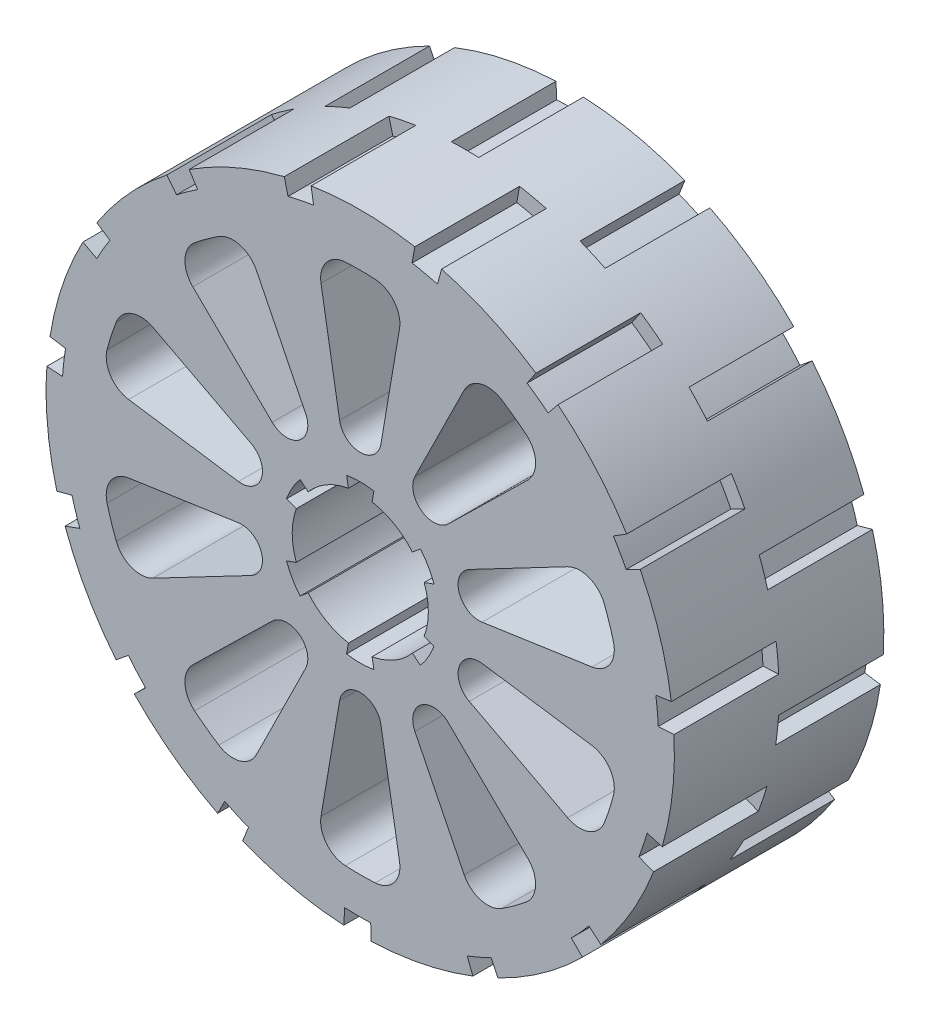
SolidWorks part; units mm, degrees
material "Silicon Rubber"
ref_plane "Plan de face" through (0, 0, 0) normal (0, 0, 1) x (1, 0, 0)
ref_plane "Plan de dessus" through (0, 0, 0) normal (0, 1, 0) x (1, 0, 0)
ref_plane "Plan de droite" through (0, 0, 0) normal (1, 0, 0) x (0, 0, -1)
sketch "Esquisse1" plane through (0, 0, 0) normal (0, 0, 1) x (1, 0, 0)
  circle A0 centre (0, 0) radius 60
  dimension "D1" = 120
extrude "Boss.-Extru.1" add sketch "Esquisse1" along normal blind 40
ref_axis "Axis1" through (0, 0, -85.4045) along (0, 0, 1)
sketch "Sketch2" plane through (0, 0, 0) normal (0, 1, 0) x (1, 0, 0)
  line L0 (0, 0) -> (-57, 0)
  line L1 (60, 0) -> (-60, 0) construction
  line L2 (-57, 0) -> (0, -15)
  line L3 (0, -15) -> (0, 0)
  line L5 (-60, 0) -> (-60, -40) construction
  dimension "D2" = 15
  dimension "D3" = 3
sketch "Sketch3" plane through (0, 0, 0) normal (0, 0, 1) x (1, 0, 0)
  line L0 (0, 60) -> (0, -60) construction
  line L1 (-3.9433, 23.1806) -> (-7.5, 44.088)
  line L2 (7.5, 44.088) -> (3.9433, 23.1806)
  circle A0 centre (0, 0) radius 60 construction
  arc A1 (-2.8565, 49.9183) -> (2.8565, 49.9183) centre (0, 0) cw
  arc A2 (7.5, 44.088) -> (2.8565, 49.9183) centre (2.5708, 44.9265) ccw
  arc A3 (-7.5, 44.088) -> (-2.8565, 49.9183) centre (-2.5708, 44.9265) cw
  arc A4 (-3.9433, 23.1806) -> (3.9433, 23.1806) centre (0, 23.8514) ccw
  point P9 (0, 50)
  dimension "D1" = 10
  dimension "D2" = 5
  dimension "D3" = 4
  dimension "D4" = 15
extrude "Cut-Extrude4" cut sketch "Sketch3" against normal through all and the other way through all
pattern_circular "CirPattern1" count 10 over 360 about axis through (0, 0, -85.4045) along (0, 0, 1) of "Cut-Extrude4"
sketch "Sketch4" plane through (0, 0, 40) normal (0, 0, 1) x (1, 0, 0)
  circle A0 centre (0, 0) radius 9
  dimension "D1" = 18
extrude "Boss-Extrude1" add sketch "Sketch4" along normal blind 10
sketch "Sketch5" plane through (0, 0, 50) normal (0, 0, 1) x (1, 0, 0)
  circle A0 centre (0, 0) radius 5
  dimension "D1" = 10
extrude "Cut-Extrude5" cut sketch "Sketch5" against normal through all
sketch "Sketch6" plane through (0, 0, 40) normal (0, 0, 1) x (1, 0, 0)
  line L0 (10.4189, 59.0885) -> (9.8979, 56.134)
  line L1 (14.7527, 55.0578) -> (15.5291, 57.9555)
  line L2 (0, 60) -> (0, 0) construction
  arc A0 (9.8979, 56.134) -> (14.7527, 55.0578) centre (0, 0) cw
  circle A1 centre (0, 0) radius 60
  arc A2 (15.5291, 57.9555) -> (10.4189, 59.0885) centre (0, 0) ccw
  circle A3 centre (0, 0) radius 60 construction
  dimension "D3" = 3
  dimension "D2" = 5
  dimension "D4" = 10
  dimension "D1" = 0
extrude "Cut-Extrude6" cut sketch "Sketch6" against normal blind 20 contours L1 A2 L0 A0 region at (12.6605, 57.1077, 40)
pattern_circular "CirPattern2" count 15 over 360 about axis through (0, 0, -85.4045) along (0, 0, 1) of "Cut-Extrude6"
sketch "Sketch7" plane through (0, 0, 0) normal (0, 0, -1) x (-1, 0, 0)
  line L0 (-2.6172, 59.9429) -> (-2.4863, 56.9457)
  line L1 (2.4863, 56.9457) -> (2.6172, 59.9429)
  line L2 (0, 60) -> (0, 0) construction
  arc A0 (-2.4863, 56.9457) -> (2.4863, 56.9457) centre (0, 0) cw
  circle A1 centre (0, 0) radius 60 construction
  arc A6 (2.6172, 59.9429) -> (-2.6172, 59.9429) centre (0, 0) ccw
  point P6 (0, 60)
  dimension "D1" = 3
  dimension "D2" = 5
extrude "Cut-Extrude7" cut sketch "Sketch7" against normal blind 20
pattern_circular "CirPattern3" count 15 over 360 about axis through (0, 0, 15) along (0, 0, -1) of "Cut-Extrude7" reverse direction yes
sketch "Sketch8" plane through (0, 0, 40) normal (0, 0, 1) x (1, 0, 0)
  line L0 (-2.6047, 14.7721) -> (-2.2574, 12.8025)
  line L1 (2.6047, 14.7721) -> (2.2574, 12.8025)
  line L2 (0, 15) -> (0, 0) construction
  line L3 (11.4907, 9.6418) -> (9.9586, 8.3562)
  line L4 (14.0954, 5.1303) -> (12.216, 4.4463)
  line L5 (14.0954, -5.1303) -> (12.216, -4.4463)
  line L6 (11.4907, -9.6418) -> (9.9586, -8.3562)
  line L7 (2.6047, -14.7721) -> (2.2574, -12.8025)
  line L8 (-2.6047, -14.7721) -> (-2.2574, -12.8025)
  line L9 (-11.4907, -9.6418) -> (-9.9586, -8.3562)
  line L10 (-14.0954, -5.1303) -> (-12.216, -4.4463)
  line L12 (-14.0954, 5.1303) -> (-12.216, 4.4463)
  line L13 (-11.4907, 9.6418) -> (-9.9586, 8.3562)
  circle A3 centre (0, 0) radius 15 construction
  arc A7 (-12.216, 4.4463) -> (-12.216, -4.4463) centre (0, 0) ccw
  arc A10 (-2.6047, 14.7721) -> (2.6047, 14.7721) centre (0, 0) cw
  arc A11 (11.4907, 9.6418) -> (14.0954, 5.1303) centre (0, 0) cw
  arc A12 (14.0954, -5.1303) -> (11.4907, -9.6418) centre (0, 0) cw
  arc A13 (2.6047, -14.7721) -> (-2.6047, -14.7721) centre (0, 0) cw
  arc A14 (-11.4907, -9.6418) -> (-14.0954, -5.1303) centre (0, 0) cw
  arc A15 (-14.0954, 5.1303) -> (-11.4907, 9.6418) centre (0, 0) cw
  circle A17 centre (0, 0) radius 13 construction
  arc A18 (-9.9586, -8.3562) -> (-2.2574, -12.8025) centre (0, 0) ccw
  arc A19 (2.2574, -12.8025) -> (9.9586, -8.3562) centre (0, 0) ccw
  arc A20 (12.216, -4.4463) -> (12.216, 4.4463) centre (0, 0) ccw
  arc A21 (9.9586, 8.3562) -> (2.2574, 12.8025) centre (0, 0) ccw
  arc A22 (-2.2574, 12.8025) -> (-9.9586, 8.3562) centre (0, 0) ccw
  point P34 (0, 0)
  dimension "D1" = 30
  dimension "D2" = 2
  dimension "D3" = 20
  dimension "D4" = 6
extrude "Cut-Extrude8" cut sketch "Sketch8" against normal through all both and the other way through all
